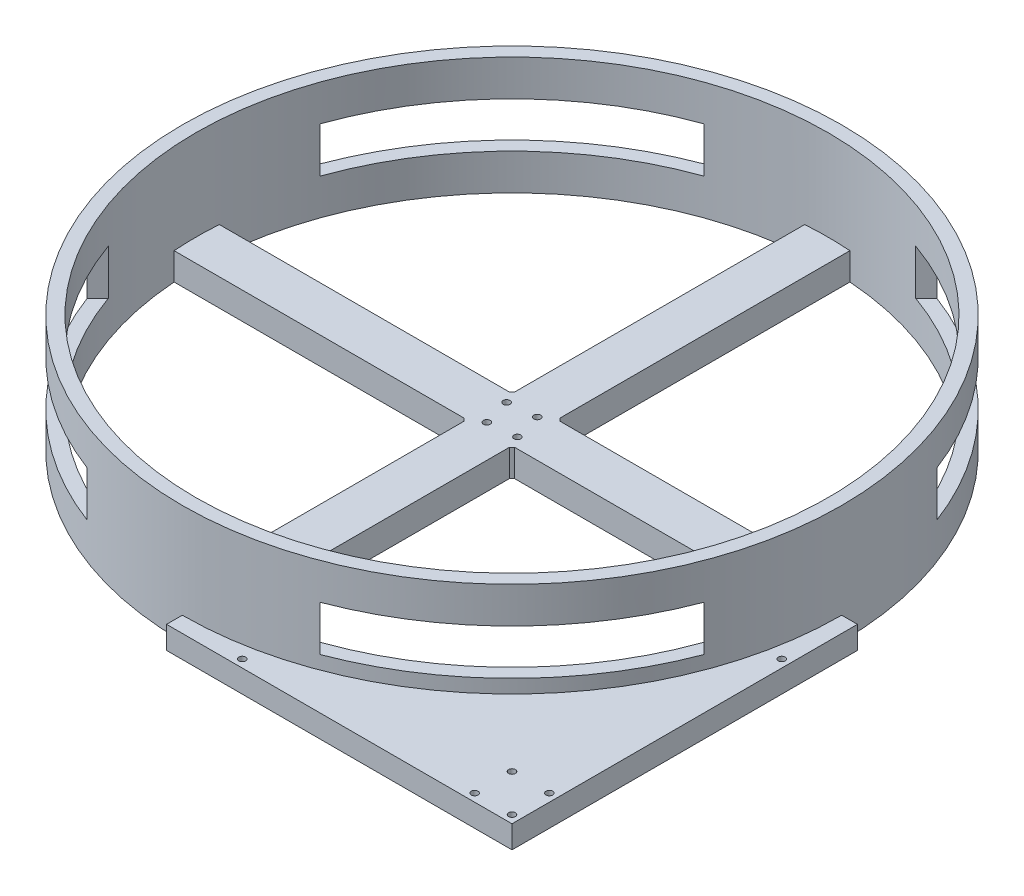
SolidWorks part; units mm, degrees
ref_plane "Front Plane" through (0, 0, 0) normal (0, 0, 1) x (1, 0, 0)
ref_plane "Top Plane" through (0, 0, 0) normal (0, 1, 0) x (1, 0, 0)
ref_plane "Right Plane" through (0, 0, 0) normal (1, 0, 0) x (0, 0, -1)
sketch "Sketch1" plane through (0, 0, 0) normal (0, 1, 0) x (1, 0, 0)
  line L0 (0, 0) -> (152.6644, 152.6644) construction
  line L2 (-152.6644, 152.6644) -> (0, 0) construction
  circle A0 centre (0, 0) radius 215.9 construction
  circle A1 centre (-152.6644, 152.6644) radius 139.7
  circle A5 centre (-152.6644, 152.6644) radius 145.7
  dimension "D1" = 431.8
  dimension "D4" = 279.4
  dimension "D2" = 90
  dimension "D6" = 6
extrude "Boss-Extrude1" add sketch "Sketch1" along normal blind 60
ref_plane "Plane1" through (0, 8, 0) normal (0, -1, 0) x (-1, 0, 0)
sketch "Sketch2" plane through (0, 8, 0) normal (0, -1, 0) x (-1, 0, 0)
  line L0 (142.6644, 137.6644) -> (142.6644, 13.3227)
  line L1 (152.6644, 152.6644) -> (152.6644, 157.6644) construction
  line L2 (162.6644, 137.6644) -> (162.6644, 13.3227)
  line L3 (162.6644, 137.6644) -> (162.6644, 12.9644) construction
  line L4 (142.6644, 137.6644) -> (142.6644, 12.9644) construction
  line L5 (162.6644, 167.6644) -> (162.6644, 292.006)
  line L6 (142.6644, 167.6644) -> (142.6644, 292.006)
  line L7 (162.6644, 167.6644) -> (162.6644, 292.3644) construction
  line L8 (142.6644, 167.6644) -> (142.6644, 292.3644) construction
  line L9 (162.6644, 137.6644) -> (162.6644, 141.484)
  line L10 (142.6644, 137.6644) -> (142.6644, 141.484)
  line L11 (162.6644, 163.8447) -> (162.6644, 167.6644)
  line L12 (142.6644, 163.8447) -> (142.6644, 167.6644)
  line L13 (137.6644, 162.6644) -> (13.3227, 162.6644)
  line L14 (137.6644, 142.6644) -> (13.3227, 142.6644)
  line L15 (162.6644, 167.6644) -> (162.6644, 292.006)
  line L16 (142.6644, 167.6644) -> (142.6644, 292.006)
  line L17 (167.6644, 142.6644) -> (292.006, 142.6644)
  line L18 (167.6644, 162.6644) -> (292.006, 162.6644)
  line L19 (167.6644, 142.6644) -> (163.8447, 142.6644)
  line L20 (167.6644, 162.6644) -> (163.8447, 162.6644)
  line L21 (137.6644, 142.6644) -> (141.484, 142.6644)
  line L24 (137.6644, 162.6644) -> (141.484, 162.6644)
  line L28 (152.6644, 167.6644) -> (152.6644, 292.3644) construction
  line L38 (152.6644, 137.6644) -> (152.6644, 12.9644) construction
  circle A0 centre (152.6644, 152.6644) radius 139.7 construction
  circle A1 centre (152.6644, 152.6644) radius 139.7
  circle A2 centre (152.6644, 152.6644) radius 15
  point P0 (152.6644, 152.6644)
  dimension "D4" = 30
  dimension "D1" = 10
  dimension "D2" = 10
  dimension "D3" = 10
  dimension "D5" = 10
  dimension "D6" = 4
extrude "Boss-Extrude2" add sketch "Sketch2" against normal blind 12 contours A2 A1 | A2 A1 | A2 A1 | A2 A1 | A2 region at (-152.6644, 8, -75.9791) region at (-152.6644, 8, -152.6644) region at (-75.9791, 8, -152.6644) region at (-229.3496, 8, -152.6644) region at (-152.6644, 8, -229.3496)
sketch "Sketch3" plane through (0, 8, 0) normal (0, -1, 0) x (-1, 0, 0)
  line L0 (0, 0) -> (0, 346.8025) construction
  line L1 (0, 0) -> (369.9988, 0) construction
  line L2 (152.6644, 6.9644) -> (152.6644, 0)
  line L3 (6.9644, 152.6644) -> (0, 152.6644)
  line L4 (152.6644, 0) -> (0, 0)
  line L5 (0, 0) -> (0, 152.6644)
  circle A0 centre (152.6644, 152.6644) radius 145.7 construction
  arc A1 (6.9644, 152.6644) -> (152.6644, 6.9644) centre (152.6644, 152.6644) ccw
  point P3 (0, 0)
extrude "Boss-Extrude3" add sketch "Sketch3" against normal blind 10
sketch "Sketch4" plane through (0, 18, 0) normal (0, 1, 0) x (1, 0, 0)
  line L0 (-152.6644, 0) -> (-152.6644, 6.9644) construction
  line L1 (-152.6644, 3.4822) -> (-3.4822, 3.4822) construction
  line L2 (0, 152.6644) -> (0, 0) construction
  line L3 (-3.4822, 152.6644) -> (-3.4822, 3.4822) construction
  line L4 (-6.9644, 152.6644) -> (0, 152.6644) construction
  circle A0 centre (-122.6644, 3.4822) radius 1.5
  circle A1 centre (-20, 3.4822) radius 1.5
  circle A2 centre (-20, 20.0022) radius 1.5
  circle A3 centre (-3.4822, 20.0022) radius 1.5
  circle A4 centre (-3.4822, 3.4822) radius 1.5
  circle A5 centre (-3.4822, 122.6644) radius 1.5
  point P0 (-20, 20.0022)
  point P1 (-122.6644, 3.4822)
  point P2 (-3.4822, 122.6644)
  point P3 (-20, 3.4822)
  point P4 (-3.4822, 20.0022)
  point P5 (-152.6644, 3.4822)
  dimension "D1" = 3
  dimension "D4" = 3
  dimension "D5" = 3
  dimension "D6" = 3
  dimension "D8" = 3
  dimension "D9" = 3
  dimension "D2" = 30
  dimension "D3" = 20
  dimension "D7" = 30
  dimension "D10" = 16.52
extrude "Cut-Extrude1" cut sketch "Sketch4" against normal blind 62
extrude "Cut-Extrude2" cut sketch "Sketch1<2>" along normal up to surface (8 mm away) up to face at (-122.6644, 8, -4.9822)
sketch "Sketch1<2>" plane through (0, 0, 0) normal (0, 1, 0) x (1, 0, 0) same geometry as "Sketch1"
ref_plane "Plane2" through (-255.6898, 0, -255.6898) normal (-0.7071, 0, -0.7071) x (0, -1, 0)
sketch "Sketch5" plane through (-255.6898, 0, -255.6898) normal (-0.7071, 0, -0.7071) x (0, -1, 0)
  line L2 (-60, 0) -> (-8, 0) construction
  line L6 (-24, -60) -> (-44, -60)
  line L7 (-24, -60) -> (-24, 60)
  line L8 (-24, 60) -> (-44, 60)
  line L9 (-44, -60) -> (-44, 60)
  line L10 (-24, -60) -> (-44, 60) construction
  line L11 (-24, 60) -> (-44, -60) construction
  point P0 (-60, 0)
  point P1 (-34, 0)
  point P8 (-34, 0)
  dimension "D1" = 20
  dimension "D2" = 120
extrude "Cut-Extrude3" cut sketch "Sketch5" against normal blind 55
pattern_circular "CirPattern1" count 4 over 360 about axis through (-152.6644, 20, -152.6644) along (0, -1, 0) of "Cut-Extrude3"
sketch "Sketch6" plane through (0, 20, 0) normal (0, 1, 0) x (1, 0, 0)
  arc A0 (-159.519, 159.2419) -> (-161.2242, 156.785) centre (-160.4689, 158.0809) ccw construction
  arc A1 (-161.2242, 156.785) -> (-159.519, 159.2419) centre (-160.4689, 158.0809) ccw construction
  arc A2 (-144.1045, 148.5438) -> (-145.8097, 146.0869) centre (-144.8598, 147.2478) ccw construction
  arc A3 (-145.8097, 146.0869) -> (-144.1045, 148.5438) centre (-144.8598, 147.2478) ccw construction
  arc A4 (-158.0808, 144.8598) -> (-158.0809, 144.8598) centre (-157.2257, 146.0921) ccw construction
  arc A5 (-147.2479, 160.4689) -> (-147.2478, 160.4689) centre (-148.103, 159.2366) ccw construction
  arc A6 (-159.519, 159.2419) -> (-161.2242, 156.785) centre (-160.4689, 158.0809) ccw
  arc A7 (-161.2242, 156.785) -> (-159.519, 159.2419) centre (-160.4689, 158.0809) ccw
  arc A8 (-144.1045, 148.5438) -> (-145.8097, 146.0869) centre (-144.8598, 147.2478) ccw
  arc A9 (-145.8097, 146.0869) -> (-144.1045, 148.5438) centre (-144.8598, 147.2478) ccw
  arc A10 (-158.0808, 144.8598) -> (-158.0809, 144.8598) centre (-157.2257, 146.0921) ccw
  arc A11 (-147.2479, 160.4689) -> (-147.2478, 160.4689) centre (-148.103, 159.2366) ccw
  circle A12 centre (-157.2257, 146.0921) radius 1.5
  circle A13 centre (-148.103, 159.2366) radius 1.5
extrude "Cut-Extrude4" cut sketch "Sketch6" against normal blind 37 contours A8 A9 | A10 A12 | A11 A13 | A6 A7 region at (-160.4689, 20, -158.0809) region at (-144.8598, 20, -147.2478) region at (-157.2257, 20, -146.0921) region at (-148.103, 20, -159.2366)
